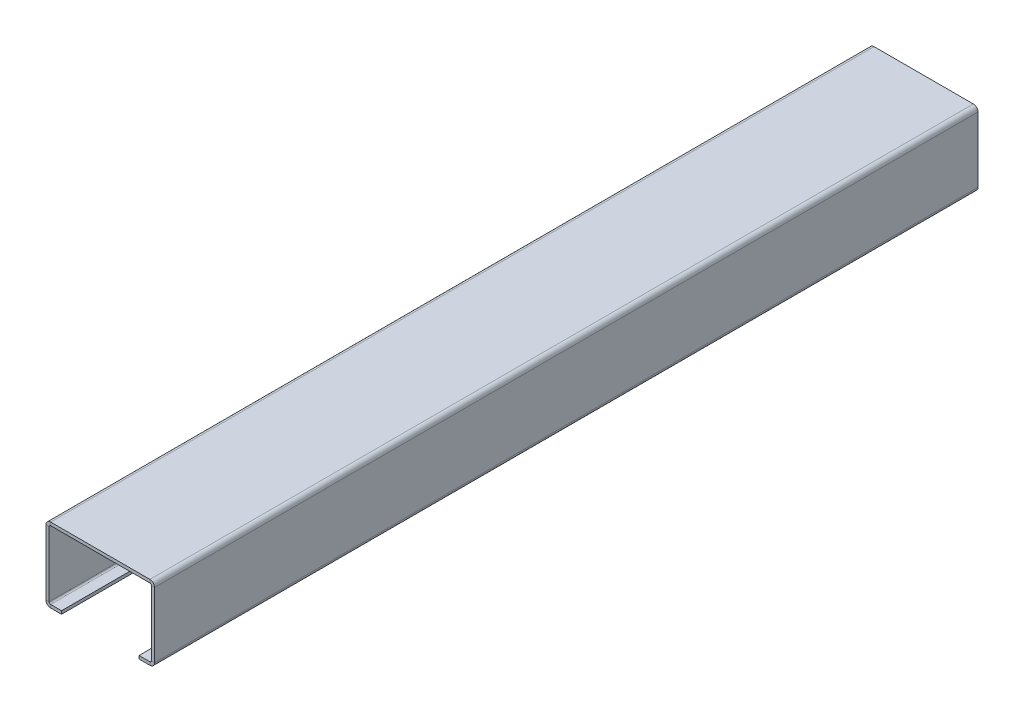
SolidWorks part; units mm, degrees
note: The reader was unsure of these and kept them because the rebuilt part matched: flange length of "Edge-Flange1", "Edge-Flange2".
ref_plane "Front Plane" through (0, 0, 0) normal (0, 0, 1) x (1, 0, 0)
ref_plane "Top Plane" through (0, 0, 0) normal (0, 1, 0) x (1, 0, 0)
ref_plane "Right Plane" through (0, 0, 0) normal (1, 0, 0) x (0, 0, -1)
sketch "BaseFlange" plane through (0, 0, 0) normal (0, 1, 0) x (1, 0, 0)
  line L1 (35, 0) -> (-35, 0)
  line L2 (35, 0) -> (35, -531)
  line L3 (35, -531) -> (-35, -531)
  line L4 (-35, 0) -> (-35, -531)
  line L5 (35, 0) -> (-35, -531) construction
  line L6 (35, -531) -> (-35, 0) construction
  point P0 (0, -265.5)
  dimension "D1" = 70
  dimension "ChannelLength" = 531
base flange "Base-Flange1" sketch "BaseFlange" thickness 2 reverse thickness direction no parameters "D1"=1
edge flange "Edge-Flange1" sketch "Sketch10" flange profiles "Sketch10", "Sketch11" flange angle 90 flange length 48 flange position material inside bend radius 1 thickness 2 parameters "D6"=10, "D8"=0.1
sketch "Sketch10" plane through (-35, -2, 0) normal (1, 0, 0) x (0, 0, 1)
  line L1 (531, 0) -> (0, 0) construction
  line L2 (0, 0) -> (0, 46)
  line L3 (0, 46) -> (531, 46)
  line L4 (531, 46) -> (531, 0)
  line L5 (531, 0) -> (0, 0)
sketch "Sketch11" plane through (35, -2, 0) normal (-1, 0, 0) x (0, 0, -1)
  line L0 (0, 0) -> (-531, 0) construction
  line L1 (0, 0) -> (-531, 0)
  line L2 (0, 0) -> (0, 46)
  line L3 (0, 46) -> (-531, 46)
  line L4 (-531, 46) -> (-531, 0)
bend "EdgeBend1" bend radius 1 bend angle 90 parameters "D5"=1
bend "EdgeBend2" bend radius 1 bend angle 90 parameters "D5"=2
edge flange "Edge-Flange2" sketch "Sketch16" flange profiles "Sketch16", "Sketch17" flange angle 90 flange length 10 flange position material inside bend radius 1 thickness 2 parameters "D6"=10, "D8"=0.1
sketch "Sketch16" plane through (-33, -48, 0) normal (0, -1, 0) x (0, 0, -1)
  line L2 (-531, 0) -> (-531, 8)
  line L3 (-531, 8) -> (0, 8)
  line L4 (0, 8) -> (0, 0)
  line L5 (-531, 0) -> (0, 0) construction
  line L6 (-531, 0) -> (0, 0)
sketch "Sketch17" plane through (33, -48, 0) normal (0, -1, 0) x (0, 0, 1)
  line L0 (0, 0) -> (531, 0) construction
  line L1 (0, 0) -> (531, 0)
  line L2 (0, 0) -> (0, 8)
  line L3 (0, 8) -> (531, 8)
  line L4 (531, 8) -> (531, 0)
bend "EdgeBend3" bend radius 1 bend angle 90 parameters "D5"=3
bend "EdgeBend4" bend radius 1 bend angle 90 parameters "D5"=4
sketch "Bend-Lines1" [suppressed] plane through (0, 0, 0) normal (0, 1, 0) x (1, 0, 0)
sketch "Bounding-Box1" [suppressed] plane through (0, 0, 0) normal (0, 1, 0) x (1, 0, 0)
sheet metal parameters "Sheet-Metal1" thickness 2 parameters "D1"=1
flat pattern "Flat-Pattern1" [suppressed]
sketch "Bend-Lines2" plane through (0, 0, 0) normal (0, 1, 0) x (1, 0, 0)
sketch3d "Bounding-Box2" [suppressed]
  line L0 (35, -250, 0) -> (35, 250, 0) construction
  line L1 (-35, -250, 0) -> (-35, 250, 0) construction
  line L2 (35, -250, 0) -> (-35, -250, 0) construction
  line L3 (35, 250, 0) -> (-35, 250, 0) construction
sheet metal parameters "Sheet-Metal2" thickness 2 parameters "D1"=1
flat pattern "Flat-Pattern1"
sketch "Bend-Lines2" plane through (0, 0, 0) normal (0, 1, 0) x (1, 0, 0)
  line L0 (33.2017, -250) -> (33.2017, 250) construction
  line L1 (-33.2017, 250) -> (-33.2017, -250) construction
  line L2 (33.2017, -250) -> (33.2017, 250) construction
  line L3 (-33.2017, 250) -> (-33.2017, -250) construction
sketch3d "Bounding-Box2" [suppressed]
  line L0 (-81.4033, -250, 0) -> (-81.4033, 250, 0) construction
  line L1 (81.4033, -250, 0) -> (81.4033, 250, 0) construction
  line L2 (-81.4033, -250, 0) -> (81.4033, -250, 0) construction
  line L3 (-81.4033, 250, 0) -> (81.4033, 250, 0) construction
bend of the flat pattern "Flatten-<EdgeBend1>1"
bend of the flat pattern "Flatten-<EdgeBend2>1"
sheet metal parameters "Sheet-Metal3" thickness 2 parameters "D1"=1
flat pattern "Flat-Pattern1"
sketch "Bend-Lines2" plane through (0, 0, 0) normal (0, 1, 0) x (1, 0, 0)
  line L0 (33.2017, -531) -> (33.2017, 0) construction
  line L1 (-33.2017, 0) -> (-33.2017, -531) construction
  line L2 (33.2017, -531) -> (33.2017, 0) construction
  line L3 (-33.2017, 0) -> (-33.2017, -531) construction
  line L4 (77.605, -531) -> (77.605, 0) construction
  line L5 (-77.605, 0) -> (-77.605, -531) construction
  line L6 (77.605, -531) -> (77.605, 0) construction
  line L7 (-77.605, 0) -> (-77.605, -531) construction
sketch3d "Bounding-Box2" [suppressed]
  line L0 (-85.8066, -531, 0) -> (-85.8066, 0, 0) construction
  line L1 (85.8066, -531, 0) -> (85.8066, 0, 0) construction
  line L2 (-85.8066, -531, 0) -> (85.8066, -531, 0) construction
  line L3 (-85.8066, 0, 0) -> (85.8066, 0, 0) construction
bend of the flat pattern "Flatten-<EdgeBend1>1"
bend of the flat pattern "Flatten-<EdgeBend2>1"
bend of the flat pattern "Flatten-<EdgeBend3>1"
bend of the flat pattern "Flatten-<EdgeBend4>1"
